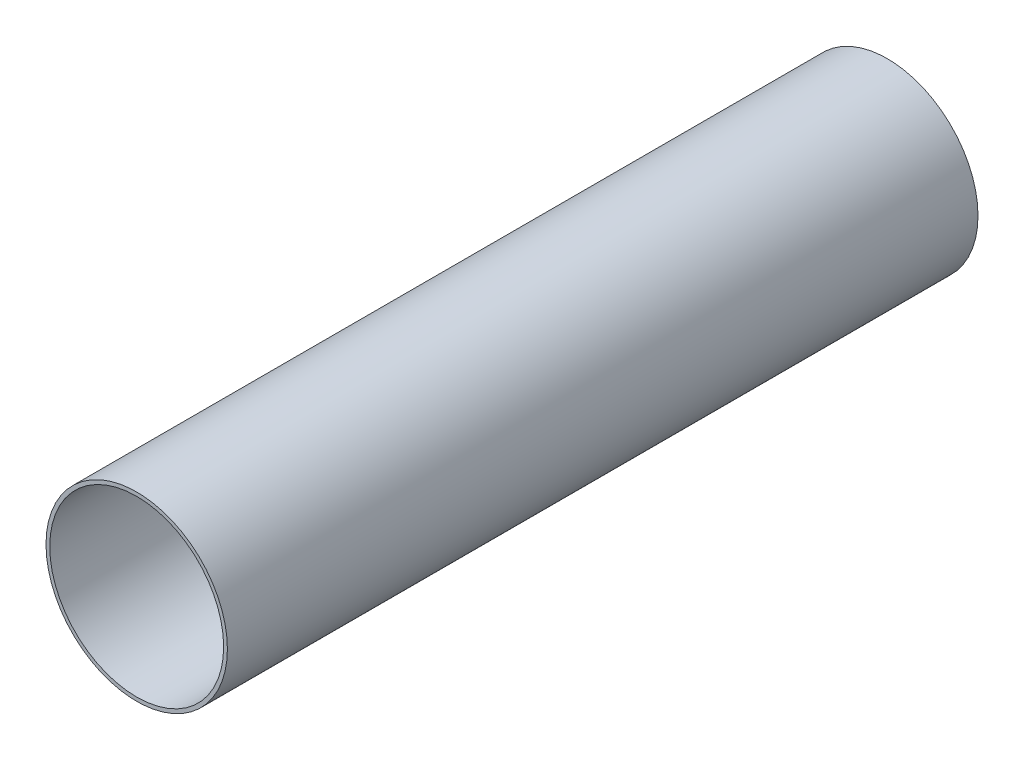
SolidWorks part; units mm, degrees
material "黄铜"
ref_plane "前视基准面" through (0, 0, 0) normal (0, 0, 1) x (1, 0, 0)
ref_plane "上视基准面" through (0, 0, 0) normal (0, 1, 0) x (1, 0, 0)
ref_plane "右视基准面" through (0, 0, 0) normal (1, 0, 0) x (0, 0, -1)
sketch "草图1" plane through (0, 0, 0) normal (0, 0, 1) x (1, 0, 0)
  circle A0 centre (0, 0) radius 13.9
  circle A1 centre (0, 0) radius 14.5
  dimension "D1" = 29
  dimension "D2" = 0.6
extrude "凸台-拉伸1" add sketch "草图1" along normal blind 120
